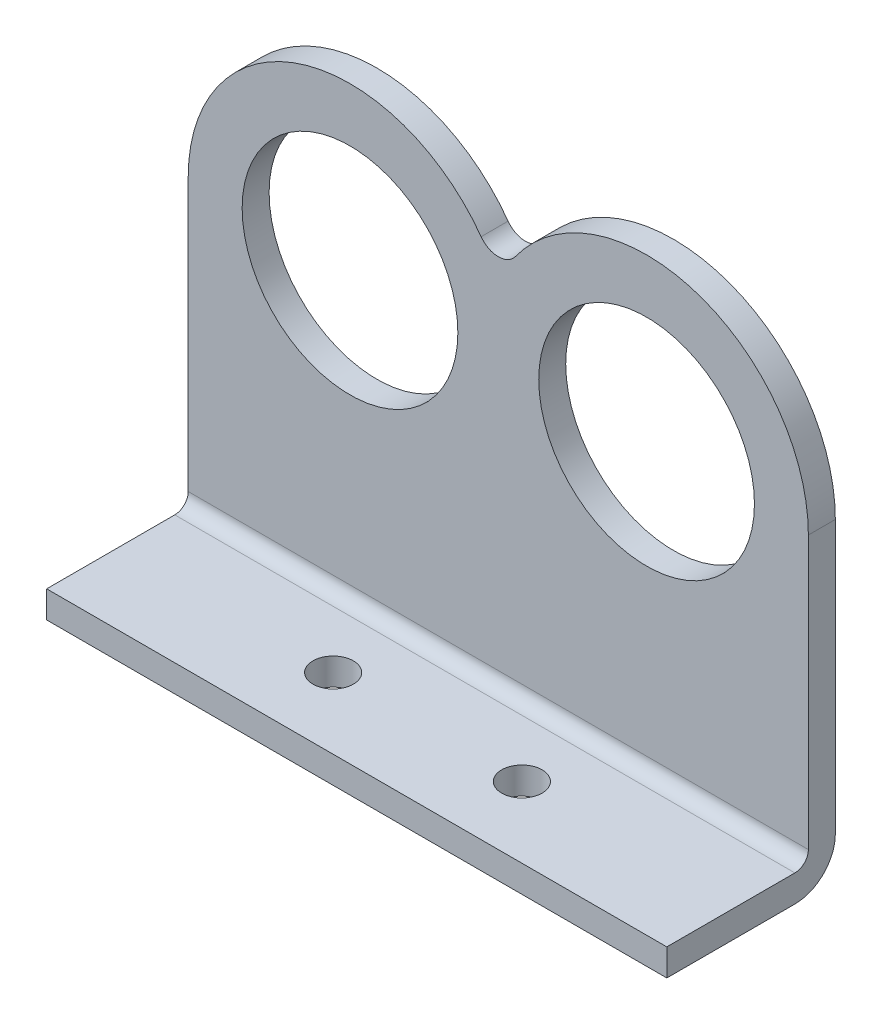
SolidWorks part; units mm, degrees
ref_plane "Front Plane" through (0, 0, 0) normal (0, 0, 1) x (1, 0, 0)
ref_plane "Top Plane" through (0, 0, 0) normal (0, 1, 0) x (1, 0, 0)
ref_plane "Right Plane" through (0, 0, 0) normal (1, 0, 0) x (0, 0, -1)
sketch "Sketch1" plane through (0, 0, 0) normal (0, 1, 0) x (1, 0, 0)
  line L1 (0, 0) -> (23, 0)
  line L2 (0, 0) -> (0, 12.5)
  line L3 (0, 12.5) -> (23, 12.5)
  line L4 (23, 0) -> (23, 12.5)
  dimension "D1" = 12.5
  dimension "D2" = 23
extrude "Boss-Extrude1" add sketch "Sketch1" along normal blind 2
sketch "Sketch2" plane through (0, 0, -12.5) normal (0, 0, -1) x (-1, 0, 0)
  line L1 (-23, 2) -> (0, 2)
  line L2 (-23, 2) -> (-23, 35.2062)
  line L3 (-23, 35.2062) -> (0, 35.2062)
  line L4 (0, 2) -> (0, 35.2062)
extrude "Boss-Extrude2" add sketch "Sketch2" against normal blind 2
sketch "Sketch3" plane through (0, 2, 0) normal (0, 1, 0) x (1, 0, 0)
  line L0 (0, 5.25) -> (23, 5.25) construction
  line L1 (0, 10.5) -> (0, 0) construction
  line L2 (23, 0) -> (23, 10.5) construction
  circle A0 centre (7, 5.25) radius 1.5
  dimension "D1" = 3
  dimension "D2" = 5.5
extrude "Cut-Extrude1" cut sketch "Sketch3" against normal blind 2 contours A0
sketch "Sketch4" plane through (0, 0, -12.5) normal (0, 0, -1) x (-1, 0, 0)
  line L1 (0, 35.2062) -> (0, 0) construction
  line L2 (0, 35.2062) -> (-23, 35.2062) construction
  circle A0 centre (-11, 23.2062) radius 8
  point P2 (-9.8668, 15.3728)
  point P3 (0, 0)
  point P4 (-10.1809, 18.5943)
  point P7 (-11, 20.2323)
  point P8 (0, 0)
  point P9 (-11, 19.1051)
  point P10 (-11, 20.214)
  dimension "D1" = 16
  dimension "D2" = 3
  dimension "D3" = 4
sketch "Sketch5" plane through (0, 0, -12.5) normal (0, 0, -1) x (-1, 0, 0)
sketch "Sketch6" plane through (0, 0, -12.5) normal (0, 0, -1) x (-1, 0, 0)
  line L0 (-23, 35.2062) -> (-23, 0) construction
  line L1 (0, 35.2062) -> (0, 0) construction
  arc A0 (-23, 23.2062) -> (-1.2728, 30.2334) centre (-11, 23.2062) cw
  arc A1 (-1.2728, 30.2334) -> (0, 29.5827) centre (0, 31.1529) ccw
extrude "Cut-Extrude2" cut sketch "Sketch4" against normal blind 2 contours A0
extrude "Cut-Extrude3" cut sketch "Sketch6" against normal blind 2 and the other way through all contours A0 A1
fillet "Fillet1" radius 3 1 edges at (11.5, 0, -12.5)
fillet "Fillet2" radius 1 1 edges at (11.5, 2, -10.5)
mirror "Mirror1" about plane through (0, 0, 0) normal (1, 0, 0) of bodies 106
